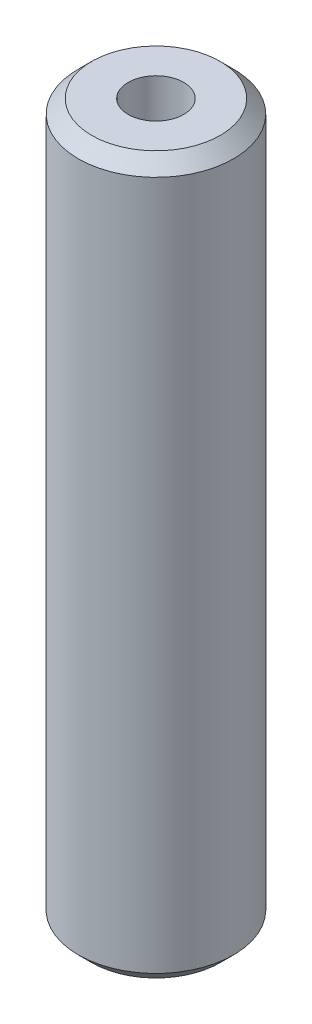
SolidWorks part; units mm, degrees
ref_plane "Front Plane" through (0, 0, 0) normal (0, 0, 1) x (1, 0, 0)
ref_plane "Top Plane" through (0, 0, 0) normal (0, 1, 0) x (1, 0, 0)
ref_plane "Right Plane" through (0, 0, 0) normal (1, 0, 0) x (0, 0, -1)
sketch "Sketch1" plane through (0, 0, 0) normal (0, 1, 0) x (1, 0, 0)
  circle A0 centre (0, 0) radius 27.5
  dimension "SHAFT_OD" = 55
extrude "Boss-Extrude1" add sketch "Sketch1" along normal blind 253.6778
sketch "Sketch2" plane through (0, 0, 0) normal (0, 1, 0) x (1, 0, 0)
  circle A0 centre (0, 0) radius 9.8391
  dimension "BORE_D" = 19.6782
extrude "Cut-Extrude1" cut sketch "Sketch2" along normal through all
chamfer "Chamfer1" distance 4.7714 angle 45 2 edges at (0, 253.6778, 27.5) (0, 0, 27.5)
